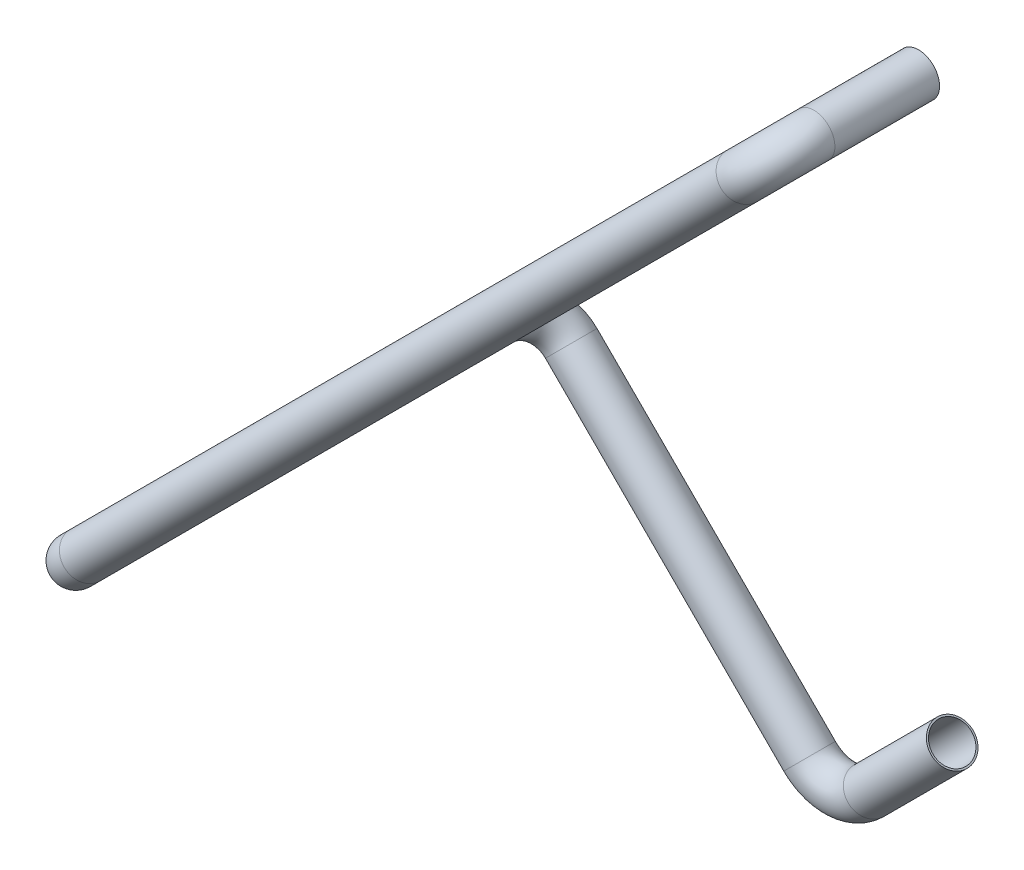
SolidWorks part; units mm, degrees
ref_plane "Front" through (0, 0, 0) normal (0, 0, 1) x (1, 0, 0)
ref_plane "Top" through (0, 0, 0) normal (0, 1, 0) x (1, 0, 0)
ref_plane "Side" through (0, 0, 0) normal (1, 0, 0) x (0, 0, -1)
sketch "PipeSketch" plane through (0, 0, 0) normal (0, 0, 1) x (1, 0, 0)
  circle A0 centre (0, 0) radius 6.35
  circle A1 centre (0, 0) radius 5.842 construction
  dimension "OuterDiameter" = 12.7
  dimension "InnerDiameter" = 11.684
sketch "FilterSketch" plane through (0, 0, 0) normal (0, 0, 1) x (1, 0, 0)
  circle A0 centre (0, 0) radius 6.35 construction
  dimension "NominalDiameter" = 12.7
sketch3d "3DSketch1"
  line L0 (0, 0, 10) -> (0, 0, 31.5419) construction
  line L1 (-8.9803, -8.9803, 44.2419) -> (-206.9051, -206.9051, 44.2419) construction
  line L2 (-215.8854, -215.8854, 31.5419) -> (-215.8854, -215.8854, -89.5299) construction
  line L3 (-206.9051, -224.8656, -102.2299) -> (-135.0631, -296.7077, -102.2299) construction
  line L4 (-99.142, -278.7471, -102.2299) -> (-117.1025, -296.7077, -102.2299) construction
  line L5 (0, 0, 0) -> (0, 0, 31.5419)
  line L6 (-8.9803, -8.9803, 44.2419) -> (-206.9051, -206.9051, 44.2419)
  line L7 (-215.8854, -215.8854, 31.5419) -> (-215.8854, -215.8854, -89.5299)
  line L8 (-206.9051, -224.8656, -102.2299) -> (-135.0631, -296.7077, -102.2299)
  line L9 (-92.071, -271.6761, -102.2299) -> (-117.1025, -296.7077, -102.2299)
  arc A0 (0, 0, 31.5419) -> (-8.9803, -8.9803, 44.2419) centre (-8.9803, -8.9803, 31.5419) ccw construction
  arc A1 (-206.9051, -206.9051, 44.2419) -> (-215.8854, -215.8854, 31.5419) centre (-206.9051, -206.9051, 31.5419) ccw construction
  arc A2 (-215.8854, -215.8854, -89.5299) -> (-206.9051, -224.8656, -102.2299) centre (-206.9051, -224.8656, -89.5299) ccw construction
  arc A3 (-135.0631, -296.7077, -102.2299) -> (-117.1025, -296.7077, -102.2299) centre (-126.0828, -287.7274, -102.2299) ccw construction
  arc A4 (0, 0, 31.5419) -> (-8.9803, -8.9803, 44.2419) centre (-8.9803, -8.9803, 31.5419) ccw
  arc A5 (-206.9051, -206.9051, 44.2419) -> (-215.8854, -215.8854, 31.5419) centre (-206.9051, -206.9051, 31.5419) ccw
  arc A6 (-215.8854, -215.8854, -89.5299) -> (-206.9051, -224.8656, -102.2299) centre (-206.9051, -224.8656, -89.5299) ccw
  arc A7 (-135.0631, -296.7077, -102.2299) -> (-117.1025, -296.7077, -102.2299) centre (-126.0828, -287.7274, -102.2299) ccw
  point P4 (0, -17.9605, 31.5419)
  point P6 (0, -17.9605, 31.5419)
  point P7 (-197.9248, -215.8854, 31.5419)
  point P10 (-215.8854, -233.8459, -89.5299)
  point P12 (-197.9248, -215.8854, 31.5419)
  point P13 (-126.0828, -287.7274, -89.5299)
  point P18 (-215.8854, -233.8459, -89.5299)
  point P24 (-126.0828, -287.7274, -89.5299)
sweep "ThinSweep" add profiles "PipeSketch" path "3DSketch1" parameters "WallThickness"=0.508
ref_plane "Plane1" through (0, 0, 0) normal (0, 0, 1) x (1, 0, 0)
ref_axis "Axis1" through (-121.5927, -301.1978, -102.2299) along (0.7071, 0.7071, 0)
ref_axis "Axis2" through (-206.9051, -224.8656, -102.2299) along (0.7071, -0.7071, 0)
ref_axis "Axis3" through (-215.8854, -215.8854, 31.5419) along (0, 0, -1)
ref_axis "Axis4" through (-4.4901, -4.4901, 44.2419) along (-0.7071, -0.7071, 0)
ref_axis "Axis5" through (0, 0, 31.5419) along (0, 0, -1)
sketch3d "3DSketch2"
  line L0 (-92.071, -271.6761, -102.2299) -> (-126.0828, -305.6879, -102.2299)
  line L1 (-126.0828, -305.6879, -102.2299) -> (-215.8854, -215.8854, -102.2299)
  line L2 (-215.8854, -215.8854, -102.2299) -> (-215.8854, -215.8854, 44.2419)
  line L3 (-215.8854, -215.8854, 44.2419) -> (0, 0, 44.2419)
  line L4 (0, 0, 44.2419) -> (0, 0, 0)
  line L5 (0, 0, 0) -> (0, 0, 31.5419) construction
  line L6 (-8.9803, -8.9803, 44.2419) -> (-206.9051, -206.9051, 44.2419) construction
  line L7 (-215.8854, -215.8854, 31.5419) -> (-215.8854, -215.8854, -89.5299) construction
  line L8 (-206.9051, -224.8656, -102.2299) -> (-135.0631, -296.7077, -102.2299) construction
  line L9 (-92.071, -271.6761, -102.2299) -> (-117.1025, -296.7077, -102.2299) construction
  point P10 (0, 0, 60.4576)
